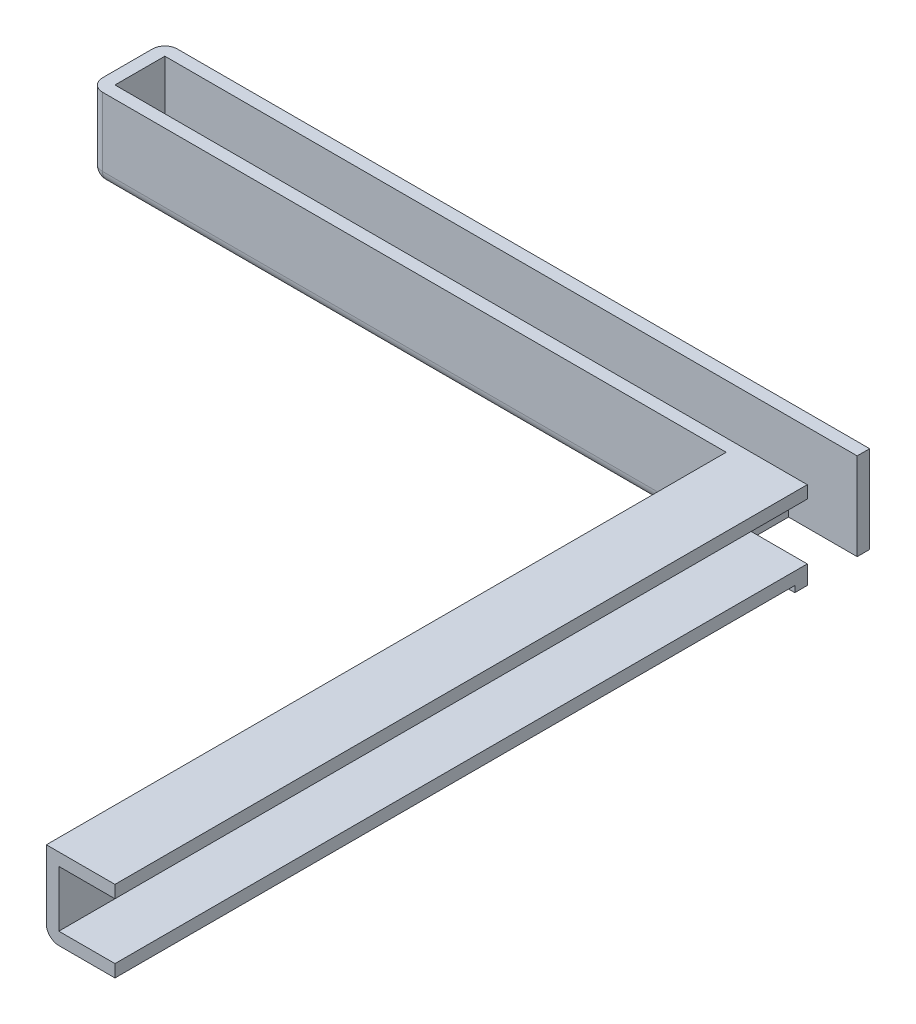
SolidWorks part; units mm, degrees
material "ABS"
ref_plane "Front Plane" through (0, 0, 0) normal (0, 0, 1) x (1, 0, 0)
ref_plane "Top Plane" through (0, 0, 0) normal (0, 1, 0) x (1, 0, 0)
ref_plane "Right Plane" through (0, 0, 0) normal (1, 0, 0) x (0, 0, -1)
sketch "Sketch1" plane through (0, 0, 0) normal (0, 1, 0) x (1, 0, 0)
  line L1 (0, 0) -> (113, 0)
  line L2 (0, 0) -> (0, -12)
  line L3 (0, -12) -> (113, -12)
  line L4 (113, 0) -> (113, -12)
  line L5 (56.5, -12) -> (56.5, 0) construction
  line L6 (0, -6) -> (113, -6) construction
  line L7 (113, -2) -> (102, -2)
  line L8 (113, -2) -> (113, -10)
  line L9 (113, -10) -> (102, -10)
  line L10 (102, -2) -> (102, -10)
  line L11 (107.5, -10) -> (107.5, -2) construction
  line L12 (113, -6) -> (102, -6) construction
  line L13 (113, 0) -> (100, 0)
  line L14 (113, 0) -> (113, -12)
  line L15 (113, -12) -> (100, -12)
  line L16 (100, 0) -> (100, -12)
  line L17 (106.5, -12) -> (106.5, 0) construction
  line L18 (113, -6) -> (100, -6) construction
  point P118 (106.5, -6)
  point P148 (107.5, -6)
  point P196 (56.5, -6)
  dimension "D1" = 113
  dimension "D2" = 12
  dimension "D3" = 11
  dimension "D4" = 8
  dimension "D5" = 2
extrude "Boss-Extrude1" add sketch "Sketch1" along normal blind 2 contours L10 L7 L4 L1 L2 L3 L9 | L16 L1 L2 L3 region at (50, 0, 6) region at (106.5, 0, 0.1769)
sketch "Sketch2" plane through (0, 2, 0) normal (0, 1, 0) x (1, 0, 0)
  line L0 (0, 0) -> (0, -12) construction
  line L1 (2, -10) -> (102, -10)
  line L2 (2, -10) -> (2, -2)
  line L3 (2, -2) -> (102, -2)
  line L4 (102, -10) -> (102, -2)
  line L5 (52, -2) -> (52, -10) construction
  line L6 (2, -6) -> (102, -6) construction
  line L8 (102, -10) -> (102, -2)
  line L9 (102, -2) -> (113, -2)
  line L10 (113, -2) -> (113, 0)
  line L11 (113, 0) -> (0, 0)
  line L12 (0, 0) -> (0, -12)
  line L13 (0, -12) -> (113, -12)
  line L14 (113, -12) -> (113, -10)
  line L15 (113, -10) -> (102, -10)
  line L16 (102, -10) -> (102, -2)
  line L17 (102, -2) -> (113, -2)
  line L18 (113, -2) -> (113, 0)
  line L19 (113, 0) -> (0, 0)
  line L21 (0, -12) -> (113, -12)
  line L22 (113, -12) -> (113, -10)
  line L23 (113, -10) -> (102, -10)
  line L31 (0, 0) -> (0, -12)
  point P4 (102, -9.7925)
  point P292 (52, -6)
  line M13 (102, -2) -> (113, -2)
  line M14 (113, -2) -> (113, 0)
  line M15 (113, 0) -> (0, 0)
  line M16 (0, 0) -> (0, -12)
  line M17 (0, -12) -> (113, -12)
  line M18 (113, -12) -> (113, -10)
  line M19 (113, -10) -> (102, -10)
  dimension "D2" = 2
  dimension "D1" = 0
extrude "Boss-Extrude2" add sketch "Sketch2" along normal blind 11 contours L2 L3 L1 M13 M14 M15 M16 M17 M18 M19 region at (52, 2, 11.1364)
sketch "Sketch3" plane through (0, 0, 12) normal (0, 0, 1) x (1, 0, 0)
  line L0 (113, 13) -> (113, 0) construction
  line L1 (113, 2) -> (104, 2)
  line L2 (113, 2) -> (113, 11)
  line L3 (113, 11) -> (104, 11)
  line L4 (104, 2) -> (104, 11)
  line L5 (108.5, 11) -> (108.5, 2) construction
  line L6 (113, 6.5) -> (104, 6.5) construction
  line L7 (0, 13) -> (113, 13) construction
  line L9 (113, 0) -> (102, 0)
  line L10 (113, 0) -> (113, 13)
  line L11 (113, 13) -> (102, 13)
  line L12 (102, 0) -> (102, 13)
  line L13 (107.5, 13) -> (107.5, 0) construction
  line L14 (113, 6.5) -> (102, 6.5) construction
  point P153 (107.5, 6.5)
  point P232 (108.5, 6.5)
  line M4 (0, 0) -> (113, 0)
  line M5 (113, 0) -> (113, 13)
  line M6 (113, 13) -> (0, 13)
  dimension "D1" = 9
  dimension "D2" = 2
  dimension "D3" = 9
  dimension "D4" = 2
extrude "Cut-Extrude1" cut sketch "Sketch3" against normal up to surface (2 mm away) contours L4 L1 L3 M5 region at (108.5, 6.5, 12) up to face at (72.3333, 5, 10)
extrude "Boss-Extrude3" add sketch "Sketch3<3>" along normal blind 109 contours L12 L1 L4 L3 M4 M5 M6 region at (112.8297, 1, 12)
sketch "Sketch3<3>" plane through (0, 0, 12) normal (0, 0, 1) x (1, 0, 0) same geometry as "Sketch3"
extrude "Boss-Extrude4" add sketch "Sketch1<3>" against normal blind 1 contours L1 L16 L3 L4 L9 L10 L7 region at (106.5, 0, 0.1769)
sketch "Sketch1<3>" plane through (0, 0, 0) normal (0, 1, 0) x (1, 0, 0) same geometry as "Sketch1"
fillet "Fillet1" radius 2 8 edges at (102, 0, 66.5) (100, -0.5, 0) (100, -0.5, 12) (0, 6.5, 0) (0, 0, 6) (0, 6.5, 12) (50, 0, 0) (50, 0, 12)
